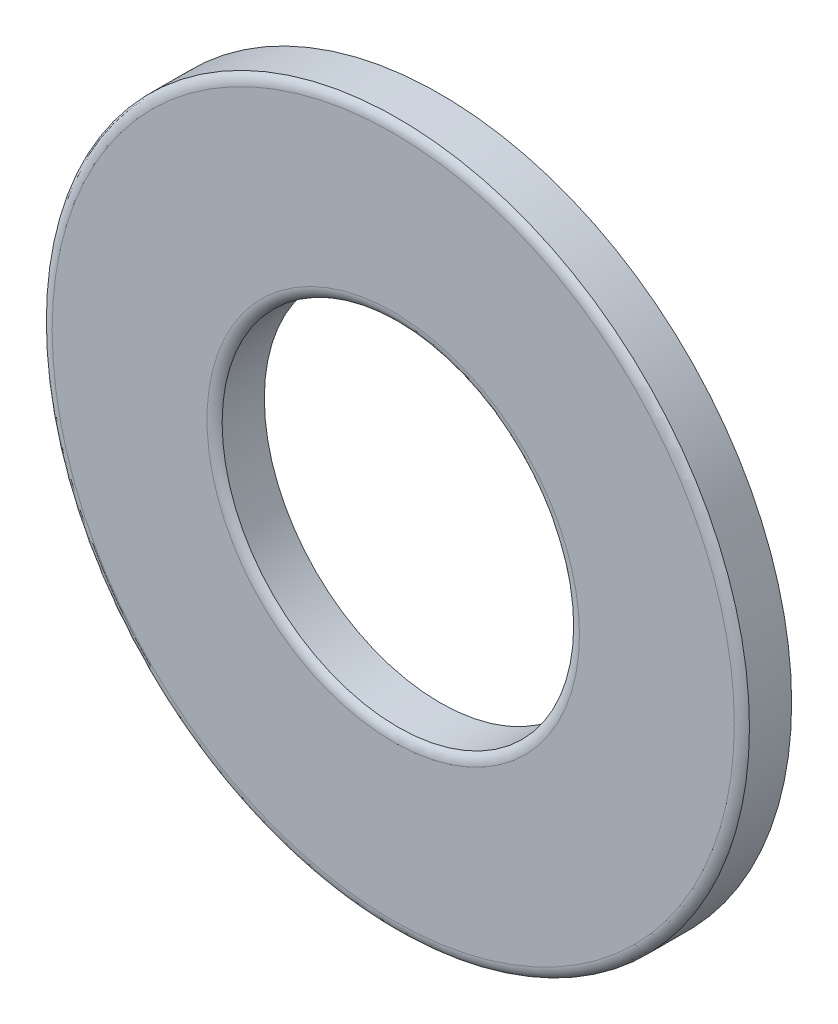
SolidWorks part; units mm, degrees
material "Plain Carbon Steel"
ref_plane "Front Plane" through (0, 0, 0) normal (0, 0, 1) x (1, 0, 0)
ref_plane "Top Plane" through (0, 0, 0) normal (0, 1, 0) x (1, 0, 0)
ref_plane "Right Plane" through (0, 0, 0) normal (1, 0, 0) x (0, 0, -1)
sketch "Sketch1" plane through (0, 0, 0) normal (0, 0, 1) x (1, 0, 0)
  circle A0 centre (0, 0) radius 9.525
  circle A1 centre (0, 0) radius 4.7625
  point P4 (4.7625, 0)
  dimension "ID" = 9.525
  dimension "OD" = 19.05
sketch "Sketch2" plane through (0, 0, 0) normal (1, 0, 0) x (0, 0, -1)
  line L0 (-0.635, 9.525) -> (0.635, 9.525)
  line L1 (0, 9.525) -> (0, 8.255) construction
  point P2 (-0.7239, 9.525)
  point P3 (0, 9.525)
  point P4 (0.7239, 9.525)
  point P8 (-0.5461, 9.525)
  point P13 (0.5461, 9.525)
  dimension "Thickness Range" = 1.27
  dimension "Thickness Range Max" = 1.4478
  dimension "Thickness Range Min" = 1.0922
sketch "Sketch3" plane through (0, 0, 0) normal (0, 0, 1) x (1, 0, 0)
  circle A0 centre (0, 0) radius 4.7625 construction
  circle A1 centre (0, 0) radius 9.525 construction
  circle A2 centre (0, 0) radius 4.7625
  circle A3 centre (0, 0) radius 9.525
extrude "Boss-Extrude1" add sketch "Sketch3" along normal up to vertex (0.635 mm away) from vertex at -0.635 starting at point (0, 9.525, -0.635)
chamfer "Chamfer1" distance 0.127 angle 30 2 edges at (9.525, 0, 0.635) (4.7625, 0, 0.635)
fillet "Fillet1" radius 0.381 2 edges at (4.8358, 0, 0.635) (9.4517, 0, 0.635)
equation "\"D1@Fillet1\"=\"D1@Chamfer1\"*3"
equation "\"D1@Chamfer1\"=\"Thickness Range@Sketch2\"*.1"
